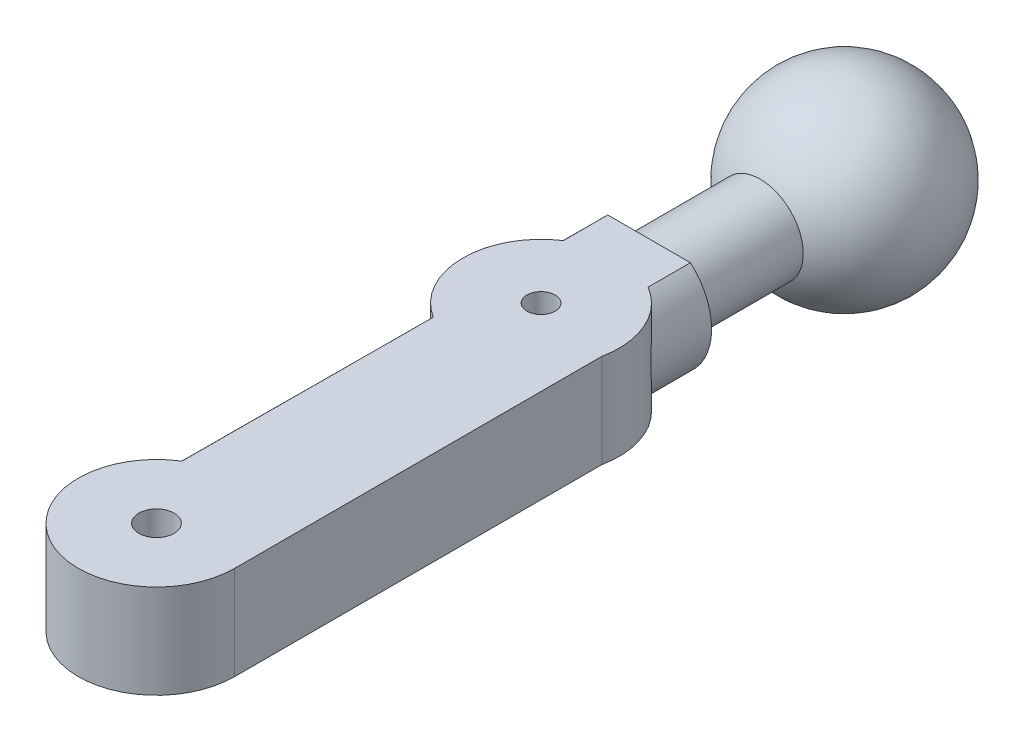
SolidWorks part; units mm, degrees
material "6061 合金"
ref_plane "前视基准面" through (0, 0, 0) normal (0, 0, 1) x (1, 0, 0)
ref_plane "上视基准面" through (0, 0, 0) normal (0, 1, 0) x (1, 0, 0)
ref_plane "右视基准面" through (0, 0, 0) normal (1, 0, 0) x (0, 0, -1)
sketch "草图1" plane through (0, 0, 0) normal (0, 0, 1) x (1, 0, 0)
  line L0 (0, 2.42) -> (0, -2.42)
  circle A0 centre (0, 0) radius 2.42
  dimension "D1" = 4.84
revolve "旋转1" add sketch "草图1" angle 360 about L0 region at (-1.0271, 0, 0)
sketch "草图2" plane through (0, 0, 0) normal (0, 0, 1) x (1, 0, 0)
  circle A0 centre (0, 0) radius 1.1
  dimension "D1" = 2.2
extrude "凸台-拉伸1" add sketch "草图2" along normal blind 17.6064
sketch "草图3" plane through (0, 0, 0) normal (0, 1, 0) x (1, 0, 0)
  line L0 (-1.1, -17.6064) -> (1.1, -17.6064) construction
  circle A0 centre (0, -17.6064) radius 2
  circle A1 centre (0, -17.6064) radius 0.45
  dimension "D1" = 0.9
  dimension "D2" = 4
extrude "切除-拉伸1" cut sketch "草图3" against normal through all both and the other way through all contours A0
extrude "凸台-拉伸2" add sketch "草图3<3>" along normal mid plane 2.4
sketch "草图3<3>" plane through (0, 0, 0) normal (0, 1, 0) x (1, 0, 0) same geometry as "草图3"
ref_axis "基准轴1" through (0, 0, 16.0148) along (0, 0, -1)
ref_plane "基准面1" through (0, 0, 14) normal (0, 0, 1) x (1, 0, 0)
sketch "草图7" plane through (0, 1.2, 0) normal (0, 1, 0) x (1, 0, 0)
  line L1 (0, -17.6064) -> (0.0411, -7.8065) construction
  line L2 (0, -16.0148) -> (0, -2.1556) construction
  line L3 (0, -17.6064) -> (2, -17.6148) construction
  line L4 (2, -17.6148) -> (2.041, -7.8149) construction
  line L5 (2.041, -7.8149) -> (0.0411, -7.8065) construction
  line L6 (0.0411, -7.8065) -> (-1.9589, -7.7981) construction
  line L7 (-1.9589, -7.7981) -> (-2, -17.598) construction
  line L8 (0, -17.6064) -> (-2, -17.598) construction
  circle A0 centre (0, -17.6064) radius 0.45 construction
  circle A1 centre (0, -17.6064) radius 0.45
  circle A2 centre (0.0411, -7.8065) radius 0.36
  circle A3 centre (0.0411, -7.8065) radius 2
  circle A4 centre (0, -17.6064) radius 2 construction
  circle A6 centre (0, -17.6064) radius 2
  circle A8 centre (0, -17.6064) radius 2
  point P19 (0.0205, -12.7064)
  dimension "D1" = 0.72
  dimension "D4" = 4
  dimension "D5" = 0.24
  dimension "D2" = 9.8
  dimension "D3" = 0
extrude "凸台-拉伸8" add sketch "草图7" against normal up to surface (2.4 mm away) contours A3 A2 region at (-1.9024, 1.2, 7.8065) up to face at (0, -1.2, 19.6064)
ref_plane "基准面2" through (0, 0, 5) normal (0, 0, 1) x (1, 0, 0)
sketch "草图9" plane through (0, 0, 5) normal (0, 0, 1) x (1, 0, 0)
  circle A0 centre (0, 0) radius 0.75
  dimension "D1" = 1.5
ref_plane "基准面3" through (0.0205, 1.2, 12.7064) normal (0.0042, 0, -1) x (-1, 0, -0.0042)
sketch "草图10" plane through (0.0205, 1.2, 12.7064) normal (0.0042, 0, -1) x (-1, 0, -0.0042)
  line L0 (0, 0) -> (0, -2.4) construction
  line L2 (-2, -2.4) -> (2, -2.4) construction
  line L3 (-2, -2.4) -> (2, -2.4)
  line L4 (2, 0) -> (-2, 0) construction
  line L5 (2, 0) -> (-2, 0)
  line L6 (-2, 0) -> (-2, -2.4)
  line L7 (2, 0) -> (2, -2.4)
  circle A0 centre (0, -1.2) radius 1.6
  dimension "D1" = 3.2
extrude "凸台-拉伸9" add sketch "草图10" along normal up to surface and the other way up to surface contours L0 L5 A0 L3 | L5 L0 L3 A0 region at (-0.7048, 0, 12.7034) region at (0.7459, 0, 12.7095) up to face at (0.0411, -1.2, 9.8065) other way up to face at (0, -1.2, 19.6064)
ref_axis "基准轴2" through (0.0411, -1.2, 7.8065) along (0, 1, 0)
ref_axis "基准轴3" through (0.0411, -1.2, 7.8065) along (0, 1, 0)
sketch "草图11" plane through (0, 1.2, 0) normal (0, 1, 0) x (1, 0, 0)
  circle A0 centre (0.0411, -7.8065) radius 0.36 construction
  circle A1 centre (0.0411, -7.8065) radius 0.36
extrude "切除-拉伸2" cut sketch "草图11" against normal through all
ref_plane "基准面4" through (0, 0, 10) normal (0, 0, 1) x (1, 0, 0)
sketch "草图12" plane through (0, 0, 10) normal (0, 0, 1) x (1, 0, 0)
  line L0 (0, 0) -> (0, 1.2)
  line L1 (2, 1.2) -> (-2, 1.2) construction
  line L2 (0, 1.2) -> (2, 1.2)
  line L3 (2, 1.2) -> (2, -1.2)
  line L4 (0, 0) -> (0, -1.2)
  line L7 (-2, -1.2) -> (2, -1.2) construction
  line L8 (0, -1.2) -> (2, -1.2)
  dimension "D1" = 2
extrude "凸台-拉伸10" add sketch "草图12" against normal up to body and the other way up to body
ref_plane "基准面5" through (0, 0, 5) normal (0, 0, 1) x (1, 0, 0)
sketch "草图13" plane through (0, 0, 5) normal (0, 0, 1) x (1, 0, 0)
  circle A0 centre (0, 0) radius 1.6
  dimension "D1" = 3.2
extrude "凸台-拉伸11" add sketch "草图13" along normal up to surface (1.5536 mm away) up to face at (-0.2627, 0.0026, 7.2857)
sketch "草图14" plane through (0, 1.2, 0) normal (0, 1, 0) x (1, 0, 0)
  line L1 (-3.6076, -3.9351) -> (3.7968, -3.9351)
  line L2 (-3.6076, -3.9351) -> (-3.6076, -7.9985)
  line L3 (-3.6076, -7.9985) -> (3.7968, -7.9985)
  line L4 (3.7968, -3.9351) -> (3.7968, -7.9985)
extrude "切除-拉伸3" cut sketch "草图14" along normal through all
sketch "草图15" plane through (0, -1.2, 0) normal (0, -1, 0) x (1, 0, 0)
  line L1 (-2.8672, 7.4299) -> (3.0311, 7.4299)
  line L2 (-2.8672, 7.4299) -> (-2.8672, 4.3824)
  line L3 (-2.8672, 4.3824) -> (3.0311, 4.3824)
  line L4 (3.0311, 7.4299) -> (3.0311, 4.3824)
extrude "切除-拉伸4" cut sketch "草图15" along normal through all
equation "\"d\"= 10"
equation "\"l\" = 13.52"
equation "\"L1\"= 8.283"
equation "\"th\"= 52.956771"
equation "\"k\"= 0.8"
equation "\"D1@凸台-拉伸1\"=\"l\"*\"k\""
equation "\"0。42\"=0.84"
equation "\"0。4\"=10"
